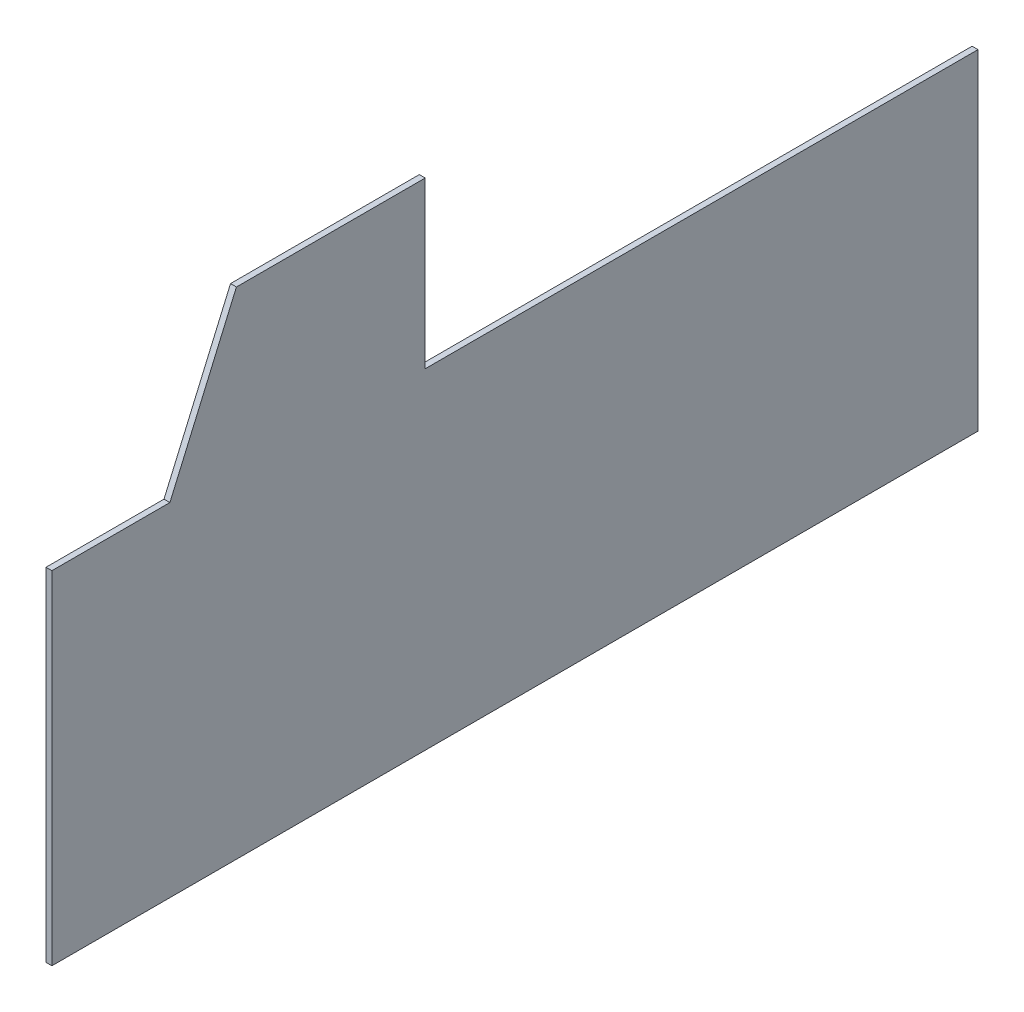
SolidWorks part; units mm, degrees
material "6061-T6 (SS)"
ref_plane "X-Y Datum" through (0, 0, 0) normal (0, 0, 1) x (1, 0, 0)
ref_plane "X-Z Datum" through (0, 0, 0) normal (0, 1, 0) x (1, 0, 0)
ref_plane "Y-Z Datum" through (0, 0, 0) normal (1, 0, 0) x (0, 0, -1)
sketch "Sketch1" plane through (0, 0, 0) normal (1, 0, 0) x (0, 0, -1)
  line L1 (-249.174, 88.9) -> (249.174, 88.9)
  line L2 (-249.174, 88.9) -> (-249.174, -88.9)
  line L3 (-249.174, -88.9) -> (249.174, -88.9)
  line L4 (249.174, 88.9) -> (249.174, -88.9)
  line L5 (-249.174, 88.9) -> (249.174, -88.9) construction
  line L6 (-249.174, -88.9) -> (249.174, 88.9) construction
  point P0 (0, 0)
  dimension "D1" = 177.8
  dimension "D2" = 498.348
extrude "Boss-Extrude1" add sketch "Sketch1" along normal mid plane 3.175
sketch "Sketch2" plane through (-1.5875, 0, 0) normal (-1, 0, 0) x (0, 0, 1)
  line L0 (249.174, 88.9) -> (249.174, -88.9) construction
  line L8 (48.2854, 88.9) -> (249.174, 88.9)
  line L9 (-249.174, 88.9) -> (249.174, 88.9) construction
  line L11 (48.2854, -88.9) -> (48.2854, 76.2)
  line L16 (249.174, 88.9) -> (249.174, 95.25)
  line L17 (249.174, 95.25) -> (185.674, 95.25)
  line L18 (185.674, 95.25) -> (149.8854, 177.8)
  line L19 (149.8854, 177.8) -> (48.2854, 177.8)
  line L20 (48.2854, 177.8) -> (48.2854, 88.9)
  line M14 (249.174, 88.9) -> (-249.174, 88.9)
  dimension "D1" = 6.35
  dimension "D2" = 63.5
  dimension "D4" = 88.9
  dimension "D5" = 101.6
extrude "Boss-Extrude2" add sketch "Sketch2" against normal blind 3.175 contours L19 L20 L16 L17 L18 M14 region at (-1.5875, 129.6106, 113.0883)
